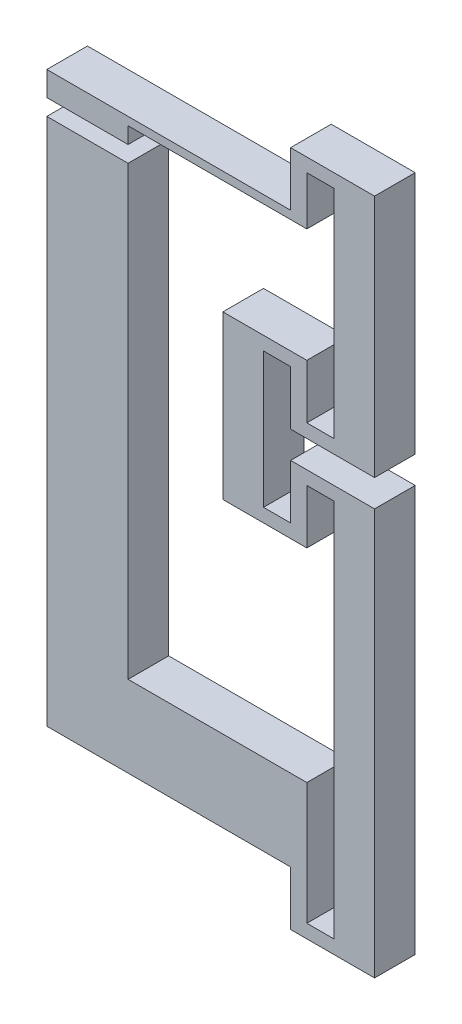
SolidWorks part; units mm, degrees
ref_plane "Front Plane" through (0, 0, 0) normal (0, 0, 1) x (1, 0, 0)
ref_plane "Top Plane" through (0, 0, 0) normal (0, 1, 0) x (1, 0, 0)
ref_plane "Right Plane" through (0, 0, 0) normal (1, 0, 0) x (0, 0, -1)
sketch "Sketch1" plane through (0, 0, 0) normal (0, 0, 1) x (1, 0, 0)
  line L0 (0, 0) -> (0, 65)
  line L4 (10, 10) -> (10, 65)
  line L5 (10, 65) -> (0, 65)
  line L6 (0, 66.9998) -> (0, 69.9998)
  line L7 (0, 69.9998) -> (30, 69.9998)
  line L8 (32, 69.9998) -> (32, 68.9998)
  line L9 (32, 68.9998) -> (10, 68.9998)
  line L10 (10, 68.9998) -> (10, 66.9998)
  line L11 (10, 66.9998) -> (0, 66.9998)
  line L12 (10, 10) -> (32, 10)
  line L20 (35.3333, -5) -> (35.3333, 41.6666)
  line L24 (40.3333, 43.3333) -> (40.3333, -6.6667)
  line L32 (21.6667, 34.9999) -> (21.6667, 54.9999)
  line L33 (21.6667, 54.9999) -> (32, 54.9999)
  line L36 (26.6667, 53.3332) -> (26.6667, 36.6666)
  line L41 (35.3333, 74.9998) -> (32, 74.9998)
  line L44 (40.3333, 76.6665) -> (40.3333, 46.6665)
  line L47 (32, 69.9998) -> (32, 74.9998)
  line L48 (30, 69.9998) -> (30, 76.6665)
  line L49 (30, 76.6665) -> (40.3333, 76.6665)
  line L55 (32, 54.9999) -> (32, 53.3332)
  line L78 (32, 48.3332) -> (35.3333, 48.3332)
  line L82 (26.6667, 53.3332) -> (30, 53.3332)
  line L83 (32, 53.3332) -> (32, 48.3332)
  line L84 (40.3333, 46.6665) -> (30, 46.6665)
  line L85 (30, 46.6665) -> (30, 53.3332)
  line L86 (21.6667, 34.9999) -> (32, 34.9999)
  line L87 (32, 34.9999) -> (32, 36.6666)
  line L88 (30, 36.6666) -> (26.6667, 36.6666)
  line L89 (40.3333, 43.3333) -> (30, 43.3333)
  line L91 (32, 41.6666) -> (35.3333, 41.6666)
  line L92 (32, 36.6666) -> (32, 41.6666)
  line L97 (40.3333, -6.6667) -> (30, -6.6667)
  line L98 (30, -6.6667) -> (30, -5)
  line L100 (30, -5) -> (30, 0)
  line L101 (35.3333, -5) -> (32, -5)
  line L105 (0, 0) -> (30, 0)
  line L106 (32, 10) -> (32, -3.1688)
  line L107 (32, -3.1688) -> (32, -5)
  line L108 (35.3333, 74.9998) -> (35.3333, 48.3332)
  line L109 (30, 43.3333) -> (30, 36.6666)
  dimension "D3" = 5
  dimension "D4" = 2
  dimension "D5" = 5
  dimension "D6" = 5
  dimension "D7" = 2
  dimension "D12" = 1
  dimension "D13" = 30
  dimension "D15" = 1
  dimension "D10" = 55
  dimension "D11" = 50
  dimension "D16" = 3.3333
  dimension "D14" = 5
  dimension "D17" = 3.3333
  dimension "D19" = 1.6667
  dimension "D21" = 10
  dimension "D23" = 2
  dimension "D24" = 30
  dimension "D25" = 3
  dimension "D22" = 10
  dimension "D18" = 1.6667
  dimension "D26" = 30
  dimension "D27" = 3.3333
  dimension "D28" = 3.3333
  dimension "D29" = 1.6667
  dimension "D30" = 1.6667
  dimension "D31" = 20
  dimension "D9" = 1.6667
  dimension "D32" = 1.6667
  dimension "D33" = 5
  dimension "D34" = 3.3333
  dimension "D20" = 5
  dimension "D8" = 2
extrude "Boss-Extrude1" add sketch "Sketch1" along normal blind 5
equation "\"A.L\"= 0.05m"
equation "\"A.h\"= 0.005m"
equation "\"A.d\"= 0.003m"
equation "\"A.delta\"= 45.0001"
equation "\"A.w\"= 0.02m"
equation "\"A.v\"= 0.03m"
equation "\"B.L\"= 0.03m"
equation "\"B.h\"= 0.005m"
equation "\"C.h\"= 0.001m"
equation "\"C.d\"= 0.003m"
equation "\"C.L\"= 0.02m"
equation "\"C.wmax\"= 0.002m"
equation "\"a_h\"= 0.002m"
equation "\"a_d\"= 0.003m"
equation "\"a_L\"= 0.005m"
equation "\"b_h\"= 0.002m"
equation "\"b_d\"= 0.003m"
equation "\"b_L\"= 0.005m"
equation "\"c_h\"= 0.002m"
equation "\"c_d\"= 0.003m"
equation "\"c_L\"= 0.005m"
equation "\"S.h\"= 0.01m"
equation "\"S.L\"= 0.0575m"
equation "\"D4@Sketch1\"=\"c_h\""
equation "\"D5@Sketch1\"=\"c_L\""
equation "\"d_h\"= 0.002m"
equation "\"d_L\"= 0.005m"
equation "\"d_d\"= 0.003m"
equation "\"D6@Sketch1\"=\"b_L\""
equation "\"D7@Sketch1\"=\"b_h\""
equation "\"D12@Sketch1\"=\"C.h\""
equation "\"D13@Sketch1\"=\"C.L\"+\"S.h\""
equation "\"D15@Sketch1\"=\"C.h\""
equation "\"A.t\"= 0.0016667m"
equation "\"A.s\"= 0.0033333m"
equation "\"D11@Sketch1\"=\"A.L\""
equation "\"D16@Sketch1\"=\"A.s\""
equation "\"D17@Sketch1\"=\"A.s\""
equation "\"D19@Sketch1\"=\"A.t\""
equation "\"D21@Sketch1\"=\"S.h\""
equation "\"D23@Sketch1\"=\"d_h\""
equation "\"D24@Sketch1\"=\"C.L\"+\"S.h\""
equation "\"D25@Sketch1\"=\"C.h\"+\"C.wmax\""
equation "\"D22@Sketch1\"=\"S.h\""
equation "\"D18@Sketch1\"=\"A.t\""
equation "\"B.t\"= 0.0016667m"
equation "\"B.s\"= 0.0033333m"
equation "\"D26@Sketch1\"=\"B.L\""
equation "\"D27@Sketch1\"=\"B.s\""
equation "\"D28@Sketch1\"=\"B.s\""
equation "\"D29@Sketch1\"=\"B.t\""
equation "\"D30@Sketch1\"=\"B.t\""
equation "\"D14@Sketch1\"=\"A.h\""
equation "\"D.L\"= 0.02m"
equation "\"D.h\"= 0.005m"
equation "\"D.s\"= 0.0033333m"
equation "\"D.t\"= 0.0016667m"
equation "\"D31@Sketch1\"=\"D.L\""
equation "\"D3@Sketch1\"=\"D.h\""
equation "\"D9@Sketch1\"=\"D.t\""
equation "\"D33@Sketch1\"=\"a_L\""
equation "\"D34@Sketch1\"=\"D.s\""
equation "\"D32@Sketch1\"=\"D.t\""
equation "\"D20@Sketch1\"=\"d_L\""
equation "\"D10@Sketch1\"=\"S.L\"-\"C.wmax\"-\"C.h\"/2"
equation "\"D8@Sketch1\"=\"d_h\""
